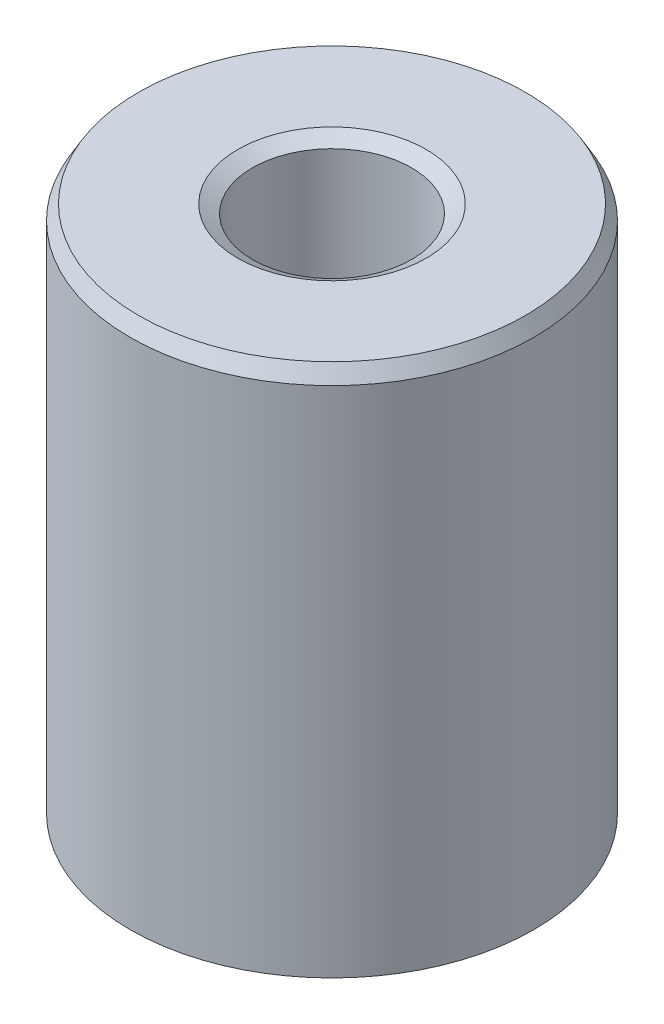
SolidWorks part; units mm, degrees
ref_plane "Front Plane" through (0, 0, 0) normal (0, 0, 1) x (1, 0, 0)
ref_plane "Top Plane" through (0, 0, 0) normal (0, 1, 0) x (1, 0, 0)
ref_plane "Right Plane" through (0, 0, 0) normal (1, 0, 0) x (0, 0, -1)
sketch "Sketch1" plane through (0, 0, 0) normal (0, 1, 0) x (1, 0, 0)
  circle A0 centre (0, 0) radius 50
  dimension "SLEEVE_OD" = 100
extrude "Boss-Extrude1" add sketch "Sketch1" along normal blind 132.7812
sketch "Sketch2" plane through (0, 0, 0) normal (0, 1, 0) x (1, 0, 0)
  circle A0 centre (0, 0) radius 19.7072
  dimension "BORE_D" = 39.4144
extrude "Cut-Extrude1" cut sketch "Sketch2" along normal through all
chamfer "Chamfer1" distance 3.6372 angle 30 4 edges at (0, 132.7812, 19.7072) (0, 0, 19.7072) (0, 0, 50) (0, 132.7812, 50) first distance on face at (0, 132.7812, 19.7072) first distance on face at (0, 0, 19.7072) first distance on face at (0, 132.7812, 50)
